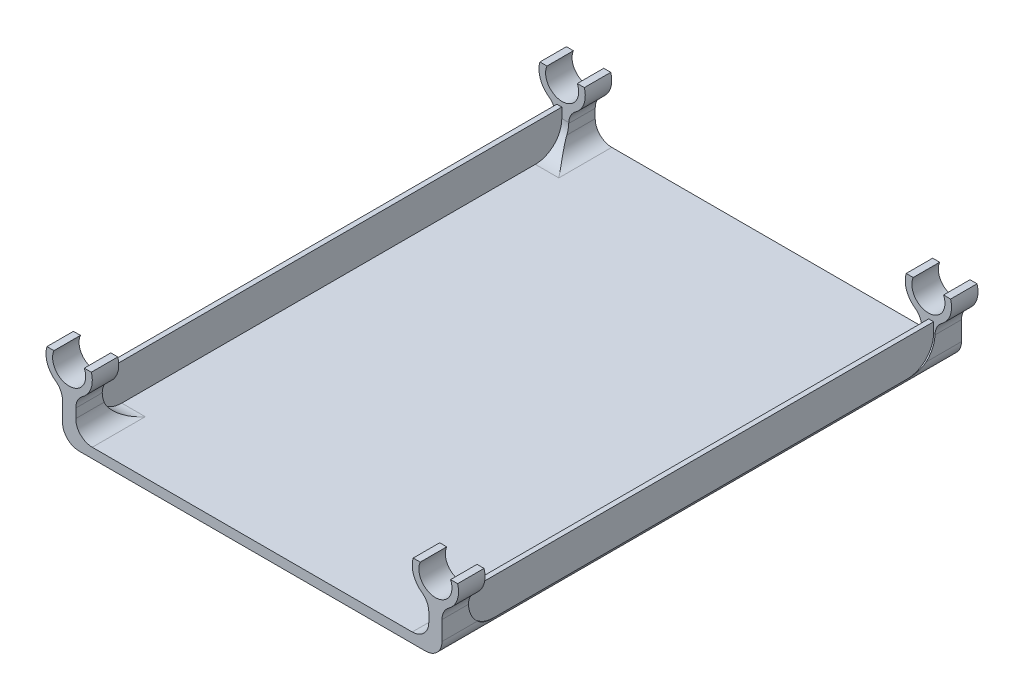
SolidWorks part; units mm, degrees
material "PLA 100% Infill"
ref_plane "Front Plane" through (0, 0, 0) normal (0, 0, 1) x (1, 0, 0)
ref_plane "Top Plane" through (0, 0, 0) normal (0, 1, 0) x (1, 0, 0)
ref_plane "Right Plane" through (0, 0, 0) normal (1, 0, 0) x (0, 0, -1)
sketch "Sketch1" plane through (0, 0, 0) normal (0, 0, 1) x (1, 0, 0)
  line L0 (-57.35, 0) -> (-57.35, 20.5) construction
  line L1 (0, 0) -> (-114.7, 0)
  line L2 (0, 0) -> (0, 2)
  line L3 (-4, 3) -> (-110.7, 3)
  line L4 (-114.7, 0) -> (-114.7, 2)
  line L5 (-53.0777, 20.5) -> (-61.6223, 20.5) construction
  line L6 (-114.7, 2) -> (-114.7, 13.7918)
  line L7 (-114.7, 13.7918) -> (-110.7, 13.7918) construction
  line L8 (-110.7, 13.7918) -> (-110.7, 3)
  line L9 (-119.4082, 22.5) -> (-117.2826, 22.5)
  line L10 (-108.1174, 22.5) -> (-105.9918, 22.5)
  line L11 (0, 2) -> (0, 13.7918)
  line L12 (-4, 13.7918) -> (-4, 3)
  line L13 (4.7082, 22.5) -> (2.5826, 22.5)
  line L14 (-6.5826, 22.5) -> (-8.7082, 22.5)
  line L15 (0, 13.7918) -> (0, 2)
  line L16 (-80.7757, 3) -> (-81.6086, 3)
  arc A0 (-117.2826, 22.5) -> (-108.1174, 22.5) centre (-112.7, 20.5) ccw
  arc A1 (-119.4082, 22.5) -> (-114.7, 13.7918) centre (-112.7, 20.5) ccw
  arc A2 (4.7082, 22.5) -> (0, 13.7918) centre (-2, 20.5) cw
  arc A3 (2.5826, 22.5) -> (-6.5826, 22.5) centre (-2, 20.5) cw
  arc A4 (-4, 13.7918) -> (-8.7082, 22.5) centre (-2, 20.5) cw
  arc A5 (-110.7, 13.7918) -> (-105.9918, 22.5) centre (-112.7, 20.5) ccw
  dimension "D2" = 10
  dimension "D6" = 3
  dimension "D1" = 20.5
  dimension "D3" = 114.7
  dimension "D4" = 2
  dimension "D5" = 4
  dimension "D7" = 2
  dimension "D8" = 2
extrude "Boss-Extrude1" add sketch "Sketch1" along normal blind 157 contours L8 A5 L10 A0 L9 A1 L6 L4 L1 L2 L11 A2 L13 A3 L14 A4 L12 L3 region at (-57.35, 1.2671, 0)
fillet "Fillet1" radius 5 8 edges at (0, 0, 78.5) (-114.7, 0, 78.5) (0, 13.7918, 78.5) (-4, 13.7918, 78.5) (-4, 3, 78.5) (-110.7, 3, 78.5) (-114.7, 13.7918, 78.5) (-110.7, 13.7918, 78.5)
sketch "Sketch2" plane through (-114.7, 0, 0) normal (-1, 0, 0) x (0, 0, 1)
  line L0 (157, 22.5) -> (0, 22.5) construction
  line L1 (8, 22.5) -> (149, 22.5)
  line L2 (8, 22.5) -> (8, 3)
  line L4 (149, 22.5) -> (149, 3)
  line L5 (0, 0) -> (-6.1147, 13.5)
  line L6 (-6.1147, 13.5) -> (-2.1147, 13.5)
  line L7 (-2.1147, 13.5) -> (1.8573, 4.7307)
  line L8 (8, 3) -> (149, 3)
  line L9 (157, 3) -> (0, 3) construction
  line L18 (78.5, 22.5) -> (76, 0) construction
  line L19 (157, 14.8144) -> (157, 22.5) construction
  line L21 (155.1728, -3.9764) -> (149.3728, -11.6599)
  line L22 (159.0753, -4.8544) -> (155.1728, -3.9764)
  line L23 (150.1463, -16.6829) -> (159.0753, -4.8544)
  line L24 (0, 0) -> (1.8573, 4.7307)
  line L25 (149.3728, -11.6599) -> (150.1463, -16.6829)
  line L26 (157, 0) -> (0, 0) construction
  line L27 (0, 22.5) -> (0, 14.8144) construction
  dimension "D1" = 8
  dimension "D2" = 8
  dimension "D6" = 4
  dimension "D7" = 13.5
extrude "Cut-Extrude1" cut sketch "Sketch2" against normal through all and the other way through all contours L2 L8 L4 L1
fillet "Fillet5" radius 8 4 edges at (-4.7087, 3, 8) (-4.7087, 3, 149) (-109.9913, 3, 149) (-109.9913, 3, 8)
ref_plane "Plane1" through (-114.2826, 0, 0) normal (-1, 0, 0) x (0, 0, 1)
sketch "Sketch4" plane through (0, 0, 8) normal (0, 0, 1) x (1, 0, 0)
  line L4 (-105.7, 3) -> (-114.2826, 3) construction
  line L5 (-114.2826, 61.8075) -> (-114.2826, -61.8075) construction
  line L6 (-57.35, 3) -> (-57.35, 0) construction
  line L7 (-114.2826, 14) -> (-112.7947, 14)
  line L8 (-114.2826, 14) -> (-114.2826, 3)
  line L9 (-114.2826, 3) -> (-112.7947, 3)
  line L10 (-112.7947, 14) -> (-112.7947, 3)
  line L11 (-114.2826, 14) -> (-112.7947, 3) construction
  line L12 (-114.2826, 3) -> (-112.7947, 14) construction
  line L13 (-9, 3) -> (-105.7, 3) construction
  line L14 (-5, 0) -> (-109.7, 0) construction
  line L15 (-1.9053, 14) -> (-1.9053, 3)
  line L16 (-0.4174, 3) -> (-1.9053, 3)
  line L17 (-0.4174, 14) -> (-0.4174, 3)
  line L18 (-0.4174, 14) -> (-1.9053, 14)
  arc A0 (-114.7, 5) -> (-109.7, 0) centre (-109.7, 5) ccw construction
  point P12 (-113.5386, 8.5)
  dimension "D1" = 11
extrude "Boss-Extrude5" add sketch "Sketch4" along normal up to surface (141 mm away) up to face at (-112.7, 16.783, 149)
